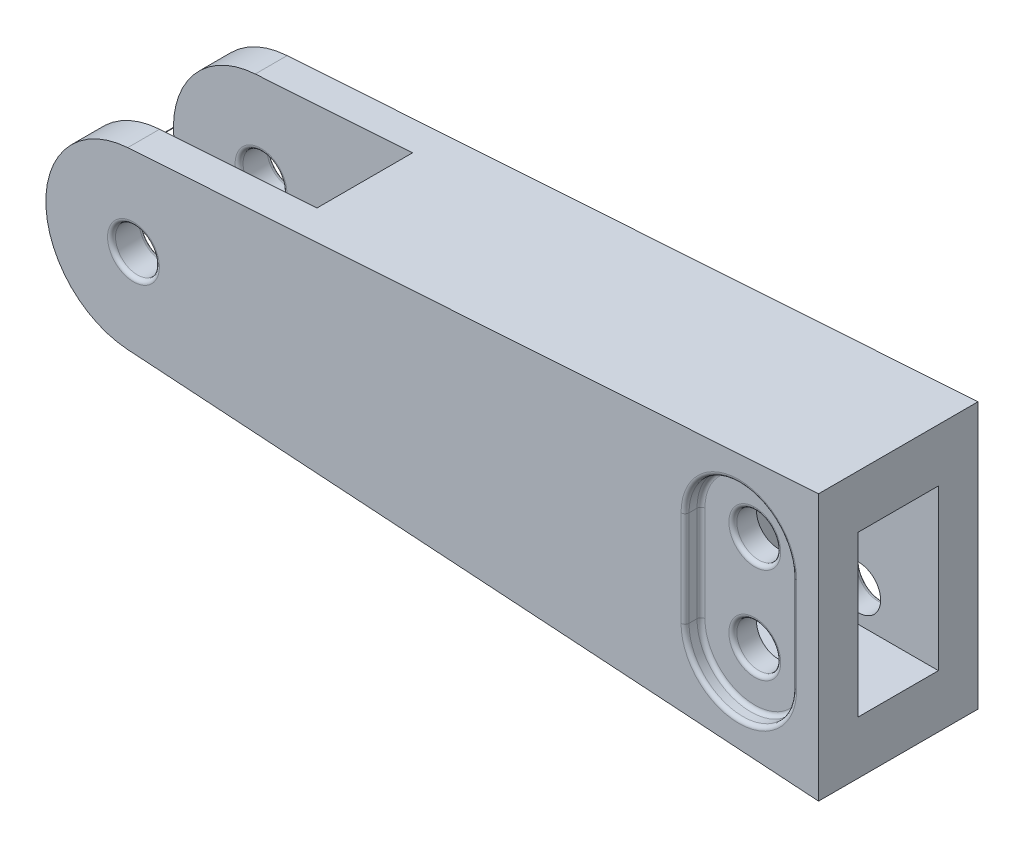
SolidWorks part; units mm, degrees
ref_plane "Front Plane" through (0, 0, 0) normal (0, 0, 1) x (1, 0, 0)
ref_plane "Top Plane" through (0, 0, 0) normal (0, 1, 0) x (1, 0, 0)
ref_plane "Right Plane" through (0, 0, 0) normal (1, 0, 0) x (0, 0, -1)
sketch "Sketch1" plane through (0, 0, 0) normal (0, 0, 1) x (1, 0, 0)
  line L1 (43.0973, 0) -> (50043.0973, 0) construction
  line L2 (0, 21.9801) -> (0, 50021.9801) construction
  line L5 (-147.5823, 10.9687) -> (-60.9237, 16.6957)
  line L6 (-60.9237, -16.6957) -> (-17.518, -19.5642) construction
  line L7 (-60.9237, 16.6957) -> (-60.9237, -16.6957) construction
  line L8 (-60.9237, 16.6957) -> (-60.9237, -16.6957)
  line L9 (-147.5823, -10.9687) -> (-60.9237, -16.6957)
  arc A1 (-147.5823, 10.9687) -> (-147.5823, -10.9687) centre (-146.8574, 0) ccw
  point P9 (0, 0)
  dimension "D1" = 146.8574
extrude "Boss-Extrude1" add sketch "Sketch1" along normal up to surface (20 mm away) contours A1 region at (-104.6886, 0, 0)
sketch "Sketch2" plane through (-60.9237, 0, 0) normal (1, 0, 0) x (0, 0, -1)
  line L0 (-10, -16.6957) -> (-10, 16.6957) construction
  line L4 (-15.035, -10.035) -> (-4.965, -10.035)
  line L5 (-15.035, -10.035) -> (-15.035, 10.035)
  line L6 (-15.035, 10.035) -> (-4.965, 10.035)
  line L7 (-20, -16.6957) -> (0, -16.6957)
  line L13 (-20, 16.6957) -> (-20, -16.6957)
  line L14 (0, 16.6957) -> (-20, 16.6957)
  line L15 (0, -16.6957) -> (0, 16.6957)
  line L16 (-20, -16.6957) -> (0, -16.6957) construction
  line L17 (-20, 16.6957) -> (-20, -16.6957) construction
  line L18 (0, 16.6957) -> (-20, 16.6957) construction
  line L19 (0, -16.6957) -> (0, 16.6957) construction
  line L20 (-4.965, -10.035) -> (-4.965, 10.035)
  line L21 (-15.035, -10.035) -> (-4.965, 10.035) construction
  line L22 (-15.035, 10.035) -> (-4.965, -10.035) construction
  line L23 (0, 0) -> (-20, 0) construction
  point P2 (-10, 0)
  point P15 (-10, 0)
  dimension "D2" = 10.07
  dimension "D3" = 20.07
  dimension "D1" = 0
extrude "Cut-Extrude1" cut sketch "Sketch2" against normal blind 20
sketch "Sketch4" plane through (0, 0, 0) normal (0, 1, 0) x (1, 0, 0)
  line L0 (-60.9237, -20) -> (-147.5823, -20) construction
  line L5 (-157.85, 0) -> (-157.85, -20) construction
  line L6 (-157.85, -4) -> (-127.85, -4)
  line L7 (-157.85, -4) -> (-157.85, -16)
  line L10 (-157.85, -16) -> (-127.85, -16)
  line L15 (-127.85, -4) -> (-127.85, -16)
  line L16 (-157.85, -4) -> (-127.85, -16) construction
  line L17 (-157.85, -16) -> (-127.85, -4) construction
  line L18 (-147.5823, 0) -> (-157.8501, 0) construction
  point P4 (-142.85, -10)
  dimension "D1" = 4
  dimension "D2" = 4
  dimension "D3" = 30
extrude "Cut-Extrude2" cut sketch "Sketch4" against normal through all both and the other way through all
sketch "Sketch5" plane through (0, 0, 0) normal (0, 0, -1) x (-1, 0, 0)
  circle A0 centre (146.8574, 0) radius 2.75
  dimension "D1" = 5.5
extrude "Cut-Extrude3" cut sketch "Sketch5" against normal through all
sketch "Sketch6" plane through (0, 0, 0) normal (0, 0, -1) x (-1, 0, 0)
  line L1 (0, 0) -> (50000, 0) construction
  line L2 (60.9237, 16.6957) -> (60.9237, -16.6957) construction
  circle A0 centre (70.9237, -6) radius 2.75
  circle A1 centre (70.9237, 6) radius 2.75
  dimension "D1" = 5.5
  dimension "D2" = 10
  dimension "D3" = 6
extrude "Cut-Extrude4" cut sketch "Sketch6" against normal through all
sketch "Sketch8" plane through (0, 0, 0) normal (0, 0, -1) x (-1, 0, 0)
  line L0 (64.1737, 6) -> (64.1737, -6)
  line L2 (77.6737, 6) -> (77.6737, -6)
  circle A0 centre (70.9237, -6) radius 2.75 construction
  circle A1 centre (70.9237, 6) radius 2.75 construction
  circle A2 centre (70.9237, -6) radius 2.75 construction
  circle A3 centre (70.9237, 6) radius 2.75 construction
  arc A4 (64.1737, -6) -> (77.6737, -6) centre (70.9237, -6) ccw
  arc A5 (77.6737, 6) -> (64.1737, 6) centre (70.9237, 6) ccw
  circle A6 centre (70.9237, 6) radius 6.75 construction
  circle A7 centre (70.9237, -6) radius 6.75 construction
  dimension "D1" = 4
extrude "Cut-Extrude5" cut sketch "Sketch8" against normal blind 2
ref_plane "Plane1" through (0, 0, 10) normal (0, 0, -1) x (-1, 0, 0)
mirror "Mirror1" about plane through (0, 0, 10) normal (0, 0, -1) of "Cut-Extrude5"
fillet "Fillet2" radius 0.5 24 edges at (-70.9237, -12.75, 2) (-64.1737, 0, 2) (-70.9237, 12.75, 2) (-70.9237, -12.75, 0) (-64.1737, 0, 0) (-70.9237, 12.75, 0) (-70.9237, -12.75, 18) (-64.1737, 0, 18) (-70.9237, 12.75, 18) (-70.9237, -12.75, 20) (-64.1737, 0, 20) (-70.9237, 12.75, 20) (-149.6074, 0, 4) (-149.6074, 0, 0) (-144.1074, 0, 16) (-149.6074, 0, 20) (-68.1737, -6, 18) (-68.1737, 6, 18) (-73.6737, -6, 2) (-73.6737, 6, 2) (-77.6737, 0, 18) (-77.6737, 0, 20) (-77.6737, 0, 2) (-77.6737, 0, 0)
